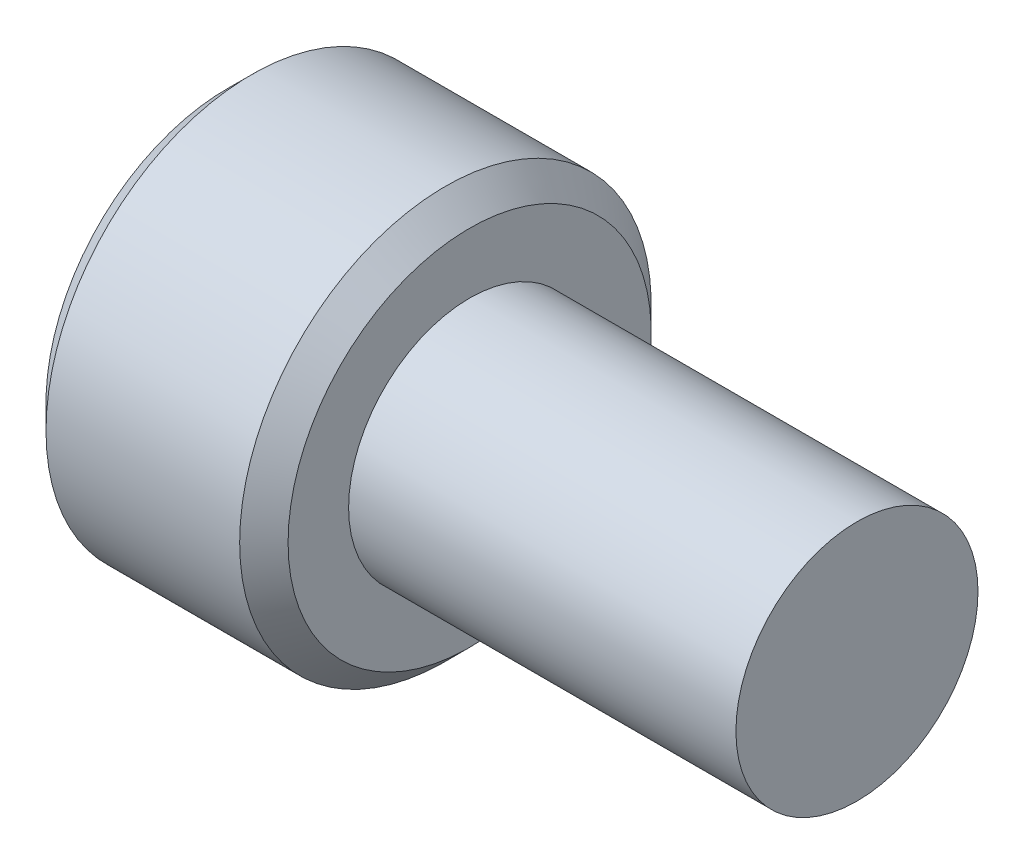
SolidWorks part; units mm, degrees
ref_plane "Front Plane" through (0, 0, 0) normal (0, 0, 1) x (1, 0, 0)
ref_plane "Top Plane" through (0, 0, 0) normal (0, 1, 0) x (1, 0, 0)
ref_plane "Right Plane" through (0, 0, 0) normal (1, 0, 0) x (0, 0, -1)
ref_axis "Axis_X" through (-10.4, 0, 0) along (1, 0, 0)
ref_axis "Axis_Y" through (0, 7.15, 0) along (0, -1, 0)
ref_axis "Axis_Z" through (0, 0, -7.15) along (0, 0, 1)
sketch "Sketch1" plane through (0, 0, 0) normal (0, 0, 1) x (1, 0, 0)
  line L0 (-5, 0) -> (8, 0) construction
  line L1 (0, 2.5) -> (8, 2.5)
  line L3 (-5, 0) -> (8, 0)
  line L4 (8, 2.5) -> (8, 0)
  line L6 (0, 2.5) -> (0, 4.25)
  line L7 (0, 4.25) -> (-5, 4.25)
  line L8 (-5, 0) -> (-5, 4.25)
  dimension "FIX_1" = 8
  dimension "FIX_3" = 5
  dimension "FIX_2" = 5
  dimension "FIX_4" = 8.5
revolve "Revolve1" add sketch "Sketch1" angle 360 about axis through (-10.4, 0, 0) along (1, 0, 0)
cosmetic thread "Thread1" parameters "FIX_7"=8, "FIX_6"=4.134
sketch "Sketch2" plane through (0, 0, 0) normal (0, 0, 1) x (1, 0, 0)
  line L0 (-1.7983, 0) -> (-3, 2)
  line L1 (-5, 0) -> (8, 0) construction
  line L2 (-3, 2) -> (-5, 2)
  line L3 (-5, 2) -> (-5, 0)
  line L4 (-5, 0) -> (-1.7983, 0) construction
  line L5 (-1.7983, 0) -> (-5, 0)
  dimension "FIX_8" = 59
  dimension "FIX_10" = 4
  dimension "FIX_9" = 2
revolve "Cut-Revolve1" cut sketch "Sketch2" angle 360 about axis through (-10.4, 0, 0) along (1, 0, 0)
sketch "Sketch3" plane through (-5, 0, 0) normal (-1, 0, 0) x (0, 0, 1)
  line L0 (0, -4.675) -> (0, 4.675) construction
  line L1 (2, 1.1547) -> (0, 2.3094)
  line L2 (0, 2.3094) -> (-2, 1.1547)
  line L3 (-2, 1.1547) -> (-2, -1.1547)
  line L4 (-2, -1.1547) -> (0, -2.3094)
  line L5 (0, -2.3094) -> (2, -1.1547)
  line L6 (2, -1.1547) -> (2, 1.1547)
  circle A0 centre (0, 0) radius 2 construction
  dimension "FIX_12" = 4
extrude "Cut-Extrude1" cut sketch "Sketch3" against normal blind 2
chamfer "Chamfer1" distance 0.5 angle 45 2 edges at (0, 0, 4.25) (-5, 0, 4.25)
equation "\"MSM_2\"=5.000000"
equation "\"MSM_3\"=5.000000"
equation "\"MSM_4\"=2.000000"
